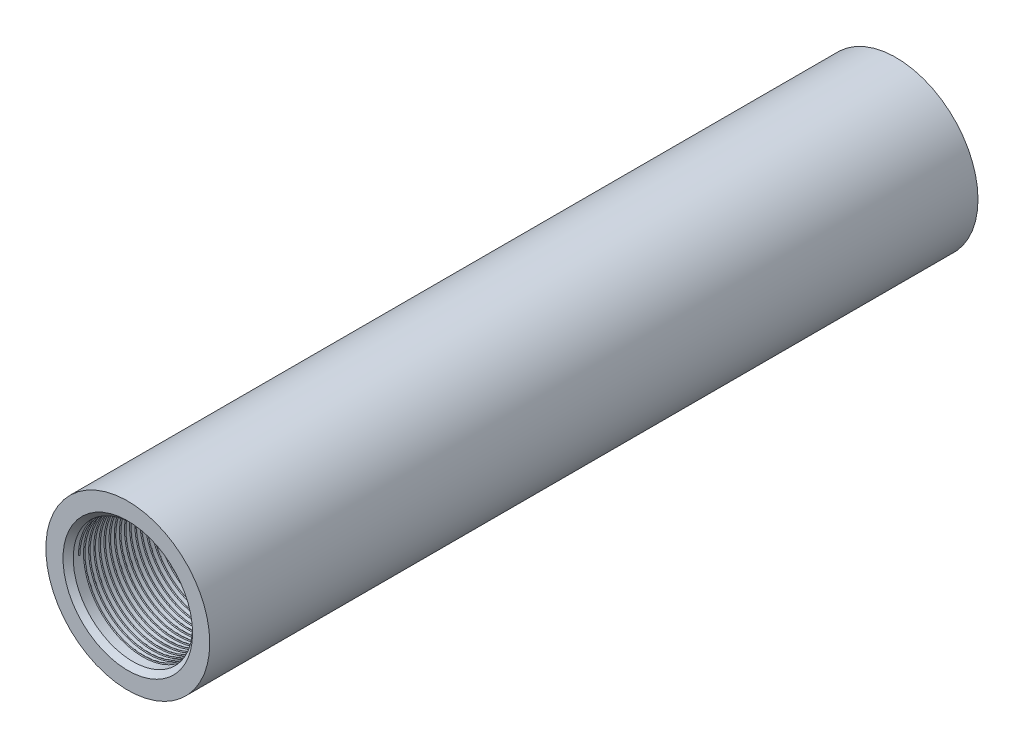
SolidWorks part; units mm, degrees
ref_plane "Ön Düzlem" through (0, 0, 0) normal (0, 0, 1) x (1, 0, 0)
ref_plane "Üst Düzlem" through (0, 0, 0) normal (0, 1, 0) x (1, 0, 0)
ref_plane "Sağ Düzlem" through (0, 0, 0) normal (1, 0, 0) x (0, 0, -1)
sketch "Çizim1" plane through (0, 0, 0) normal (0, 0, 1) x (1, 0, 0)
  circle A0 centre (0, 0) radius 16
  circle A1 centre (0, 0) radius 11.65
  dimension "D1" = 32
  dimension "D2" = 4.35
extrude "Yükseklik-Ekstrüzyon1" add sketch "Çizim1" along normal blind 150
chamfer "Pah1" distance 1 angle 45 1 edges at (11.65, 0, 150)
thread "Diş1" pitch 0.3175 method extrude profile "Diş Profili2" start angle 0, offset 1, length 20, pitch 1, diameter 23.3
ref_plane "Düzlem2" through (-11.65, 0, 148) normal (0, -1, 0) x (-1, 0, 0)
sketch "Diş Profili2" plane through (-11.65, 0, 148) normal (0, -1, 0) x (-1, 0, 0)
  line L0 (0, 0) -> (0, 0.3175) construction
  line L11 (0, 0) -> (0, 0.2778)
  line L12 (0, 0.2778) -> (-0.1719, 0.1786)
  line L13 (-0.1719, 0.1786) -> (-0.1719, 0.0992)
  line L15 (-0.1719, 0.0992) -> (0, 0)
  line L17 (-0.1719, 0.1389) -> (0, 0.1389) construction
  point P2 (0, 0)
  dimension "Pitch" = 0.3175
  dimension "Profile_Angle" = 60
  dimension "Profile_Land" = 0.0794
  dimension "Profile_Height" = 0.1719
chamfer "Pah2" distance 1 angle 45 1 edges at (11.65, 0, 0)
thread "Diş2" pitch 0.3175 method extrude profile "Diş Profili3" start angle 0, offset 0, length 20, pitch 1, diameter 23.3
ref_plane "Düzlem3" through (11.65, 0, 1) normal (0, -1, 0) x (1, 0, 0)
sketch "Diş Profili3" plane through (11.65, 0, 1) normal (0, -1, 0) x (1, 0, 0)
  line L0 (0, 0) -> (0, 0.3175) construction
  line L11 (0, 0) -> (0, 0.2778)
  line L12 (0, 0.2778) -> (-0.1719, 0.1786)
  line L13 (-0.1719, 0.1786) -> (-0.1719, 0.0992)
  line L15 (-0.1719, 0.0992) -> (0, 0)
  line L17 (-0.1719, 0.1389) -> (0, 0.1389) construction
  point P2 (0, 0)
  dimension "Pitch" = 0.3175
  dimension "Profile_Angle" = 60
  dimension "Profile_Land" = 0.0794
  dimension "Profile_Height" = 0.1719
